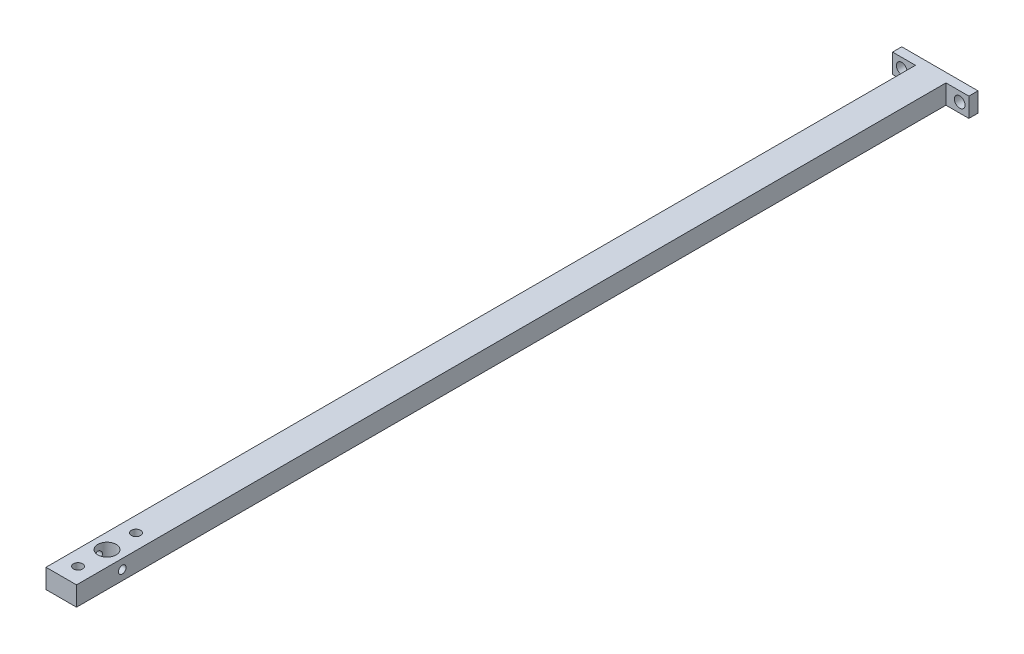
SolidWorks part; units mm, degrees
material "6061 Alloy"
ref_plane "Front Plane" through (0, 0, 0) normal (0, 0, 1) x (1, 0, 0)
ref_plane "Top Plane" through (0, 0, 0) normal (0, 1, 0) x (1, 0, 0)
ref_plane "Right Plane" through (0, 0, 0) normal (1, 0, 0) x (0, 0, -1)
sketch "Sketch1" plane through (0, 0, 0) normal (0, 1, 0) x (1, 0, 0)
  line L0 (-5, 270) -> (-5, -15)
  line L1 (-5, -15) -> (5, -15)
  line L2 (5, -15) -> (5, 270)
  line L3 (5, 270) -> (12.5, 270)
  line L4 (12.5, 270) -> (12.5, 273)
  line L5 (12.5, 273) -> (-12.5, 273)
  line L6 (-12.5, 273) -> (-12.5, 270)
  line L7 (-12.5, 270) -> (-5, 270)
  line L8 (-5, 0) -> (5, 0) construction
  line L9 (0, 273) -> (0, -15) construction
  circle A0 centre (0, -9.5) radius 1.5
  circle A1 centre (0, 9.5) radius 1.5
  circle A2 centre (0, 0) radius 3
  dimension "D1" = 19
  dimension "D6" = 6
  dimension "D7" = 3
  dimension "D8" = 3
  dimension "D2" = 9.5
  dimension "D3" = 15
  dimension "D4" = 5
  dimension "D5" = 5
  dimension "D9" = 3
  dimension "D10" = 3
  dimension "D11" = 25
  dimension "D12" = 0
  dimension "D13" = 273
extrude "Boss-Extrude1" add sketch "Sketch1" along normal blind 3.175 and the other way blind 3.175
sketch "Sketch2" plane through (0, 0, -273) normal (0, 0, -1) x (-1, 0, 0)
  line L0 (0, 3.175) -> (0, -3.175) construction
  line L1 (-12.5, 3.175) -> (12.5, 3.175) construction
  line L2 (-12.5, -3.175) -> (12.5, -3.175) construction
  line L3 (-12.5, -3.175) -> (-12.5, 3.175) construction
  circle A0 centre (-9.5, 0) radius 1.75
  circle A1 centre (9.5, 0) radius 1.75
  dimension "D1" = 3
  dimension "D3" = 3.5
  dimension "D2" = 19
extrude "Cut-Extrude1" cut sketch "Sketch2" against normal blind 3
hole_wizard "Tap Drill for M3x0.5 Tap1" positions "Sketch3" profile "Sketch4" hole size "M3x0.5" standard "ANSI Metric" end condition through all
sketch "Sketch3" plane through (5, 0, 0) normal (1, 0, 0) x (0, 0, -1)
  point P0 (0, 0)
sketch "Sketch4" plane through (5, 0, 0) normal (0, 1, 0) x (0, 0, -1)
  line L0 (0, 0) -> (0, 17.5)
  line L1 (0, 17.5) -> (1.25, 17.5)
  line L2 (1.25, 17.5) -> (1.25, 0)
  line L5 (1.25, 0) -> (0, 0)
  line L11 (0, -6.35) -> (0, 107.95) construction
  dimension "Thru Hole Dia." = 2.5
  dimension "Thru Hole Depth" = 17.5
